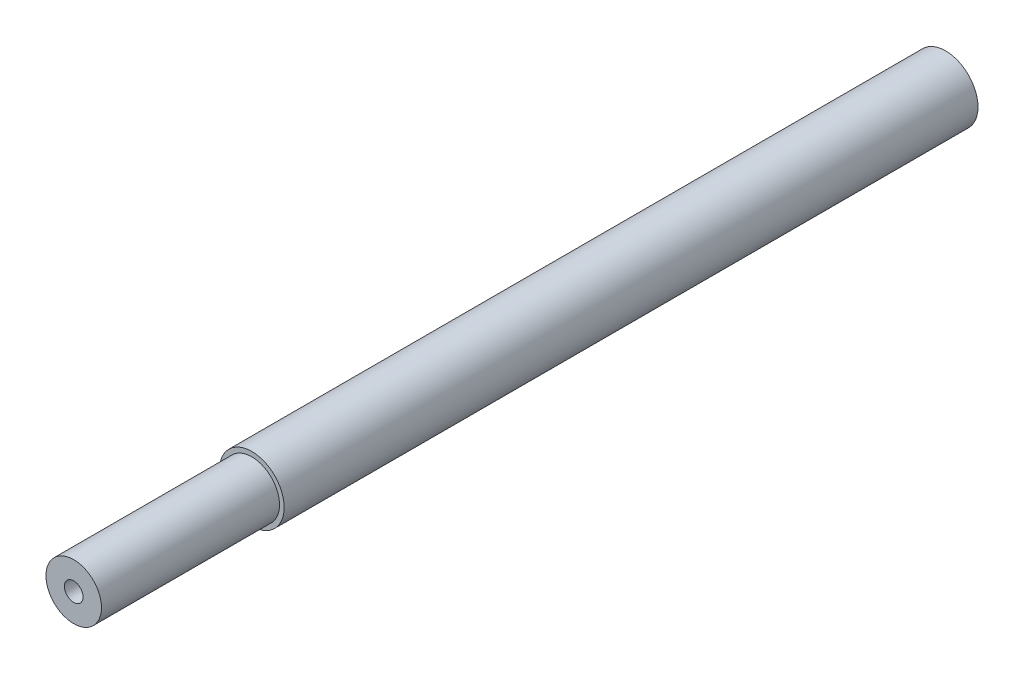
SolidWorks part; units mm, degrees
ref_plane "Front Plane" through (0, 0, 0) normal (0, 0, 1) x (1, 0, 0)
ref_plane "Top Plane" through (0, 0, 0) normal (0, 1, 0) x (1, 0, 0)
ref_plane "Right Plane" through (0, 0, 0) normal (1, 0, 0) x (0, 0, -1)
sketch "Sketch1" plane through (0, 0, 0) normal (1, 0, 0) x (0, 0, -1)
  line L0 (0, 0) -> (146.042, 0) construction
  line L1 (183, 0) -> (183, 7)
  line L3 (-5.5, 6) -> (-5.5, 0)
  line L4 (-5.5, 0) -> (183, 0)
  line L5 (-5.5, 6) -> (33, 6)
  line L6 (33, 6) -> (33, 7)
  line L7 (33, 7) -> (183, 7)
  line L8 (-6, 6) -> (-6, -6) construction
  line L9 (33, -12) -> (33, 12) construction
  line L10 (33, -45) -> (33, 45) construction
  point P9 (88.124, 11.1634)
  point P14 (33, 7.0191)
  dimension "D1" = 12
  dimension "D2" = 0.5
  dimension "D3" = 14
  dimension "D4" = 150
revolve "Revolve1" add sketch "Sketch1" angle 360 about L0
sketch "Sketch2" plane through (0, 0, 5.5) normal (0, 0, 1) x (1, 0, 0)
  circle A0 centre (0, 0) radius 2.0193
  dimension "D1" = 4.0386
extrude "Cut-Extrude1" cut sketch "Sketch2" against normal blind 25
